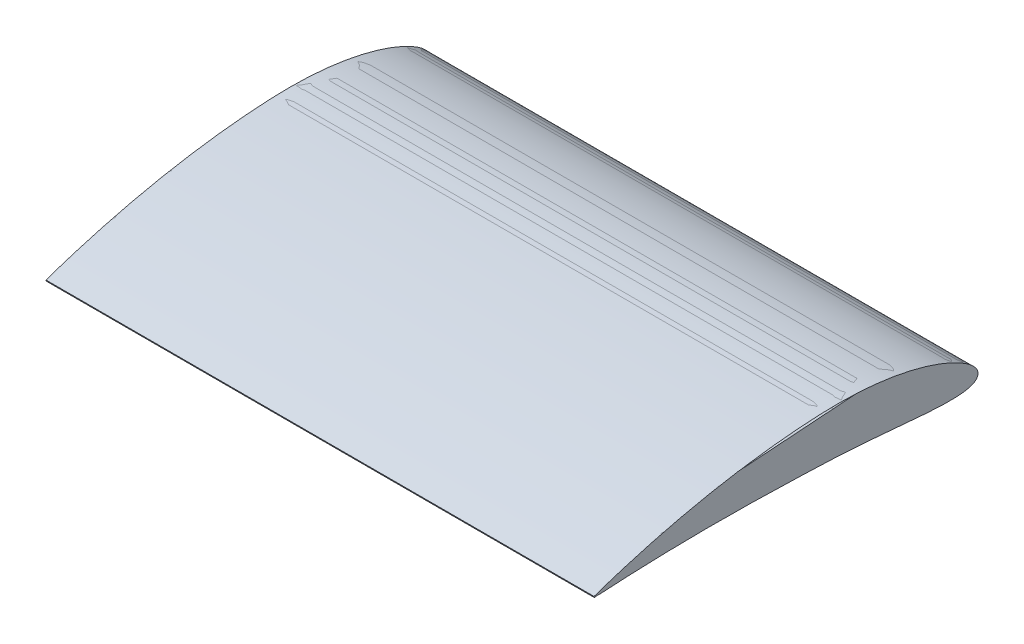
SolidWorks part; units mm, degrees
other "Markup1"
sketch "Sketch2" plane through (-254, -8.3615, 356.0294) normal (-0.9998, -0.003, 0.0177) x (0.0176, 0.0231, 0.9996)
material "E-Glass Fiber Real"
ref_plane "Front Plane" through (0, 0, 0) normal (0, 0, 1) x (1, 0, 0)
ref_plane "Top Plane" through (0, 0, 0) normal (0, 1, 0) x (1, 0, 0)
ref_plane "Right Plane" through (0, 0, 0) normal (1, 0, 0) x (0, 0, -1)
curve "Curve1"
  spline degree 3 poles (0, 0.0012, 1.0003) (0, 0.0015, 0.9994) (0, 0.0028, 0.9958) (0, 0.0055, 0.9879) (0, 0.0099, 0.9747) (0, 0.0159, 0.9565) (0, 0.0233, 0.9333) (0, 0.0318, 0.9054) (0, 0.0411, 0.8731) (0, 0.051, 0.8366) (0, 0.0612, 0.7964) (0, 0.0713, 0.7528) (0, 0.0811, 0.7063) (0, 0.0903, 0.6574) (0, 0.0985, 0.6067) (0, 0.1057, 0.5546) (0, 0.1115, 0.5018) (0, 0.1158, 0.4488) (0, 0.1186, 0.3959) (0, 0.1189, 0.3436) (0, 0.1164, 0.2927) (0, 0.1112, 0.2442) (0, 0.1037, 0.1988) (0, 0.0942, 0.157) (0, 0.0831, 0.1194) (0, 0.0711, 0.0865) (0, 0.0584, 0.0585) (0, 0.0457, 0.0357) (0, 0.0334, 0.0184) (0, 0.0218, 0.0064) (0, 0.0108, -0.0005) (0, -0.0003, -0.0011) (0, -0.0092, 0.0055) (0, -0.0148, 0.017) (0, -0.0185, 0.0329) (0, -0.0204, 0.0533) (0, -0.0208, 0.0781) (0, -0.0198, 0.107) (0, -0.0176, 0.1398) (0, -0.0147, 0.176) (0, -0.0111, 0.2153) (0, -0.0074, 0.2574) (0, -0.0037, 0.3019) (0, -0.0005, 0.3484) (0, 0.002, 0.397) (0, 0.0037, 0.4471) (0, 0.0055, 0.4983) (0, 0.0069, 0.5496) (0, 0.0079, 0.6006) (0, 0.0085, 0.6505) (0, 0.0086, 0.699) (0, 0.0083, 0.7455) (0, 0.0076, 0.7894) (0, 0.0065, 0.8302) (0, 0.0053, 0.8675) (0, 0.0039, 0.9007) (0, 0.0027, 0.9296) (0, 0.0013, 0.9539) (0, 0.0006, 0.9727) (0, -0.0011, 0.9872) (0, 0, 0.9944) (0, -0.002, 0.9999) (0, -0.0005, 1) (0, 0, 1) knots 0 0 0 0 0.001372 0.005465 0.012235 0.021602 0.033461 0.047671 0.064081 0.082496 0.102719 0.124527 0.147676 0.171913 0.196978 0.222597 0.248497 0.274385 0.300041 0.32569 0.350525 0.37428 0.396711 0.417577 0.436654 0.453744 0.46868 0.481329 0.491631 0.499616 0.505546 0.510185 0.514824 0.520702 0.528516 0.538466 0.550543 0.564643 0.580638 0.598345 0.617584 0.638174 0.659922 0.682632 0.706121 0.730727 0.7557 0.780732 0.805564 0.829932 0.85357 0.876213 0.89761 0.917519 0.935698 0.951943 0.966047 0.97784 0.987174 0.993932 0.998018 0.999386 1 1 1 1
sketch "Sketch1" plane through (0, 0, 0) normal (1, 0, 0) x (0, 0, -1)
  line L0 (-354.7873, -0.0303) -> (-354.8762, 0.4104)
  line L1 (-354.7873, -0.0303) -> (0.8093, 1.5275) construction
  line L2 (0.8093, 1.5275) -> (0.7921, 5.4415) construction
  line L3 (-354.8867, -0.0431) -> (-354.9915, 0.4765)
  spline S0 degree 1 poles (-354.9915, 0.4765) (-354.8867, -0.0431) knots 0 0 1 1 construction
  spline S1 degree 3 poles (-354.8762, 0.4104) (-354.5599, 0.5194) (-353.2997, 0.9536) (-350.4787, 1.9271) (-345.801, 3.4978) (-336.0241, 6.7216) (-319.6545, 11.7989) (-300.5983, 17.1306) (-282.4229, 21.7243) (-261.1758, 26.6516) (-238.6223, 31.1455) (-208.7748, 36.0048) (-183.9617, 39.0905) (-158.9023, 41.1132) (-140.0967, 42.1114) (-121.5167, 42.2289) (-103.4222, 41.3211) (-86.1884, 39.4787) (-70.0435, 36.8105) (-55.1998, 33.4329) (-41.8434, 29.5109) (-30.1305, 25.2201) (-20.187, 20.7343) (-12.1072, 16.2263) (-5.9269, 11.8553) (-1.6792, 7.7165) (0.7658, 3.7968) (0.9875, -0.1483) (-1.3511, -3.3089) (-5.4508, -5.2881) (-11.0873, -6.5875) (-18.3491, -7.2685) (-27.1638, -7.4049) (-37.4471, -7.0538) (-49.0831, -6.3019) (-61.9524, -5.238) (-75.9299, -3.9839) (-96.4067, -2.1536) (-117.9372, -0.4584) (-140.4848, 0.6745) (-158.2965, 1.2867) (-176.4839, 1.9179) (-200.672, 2.5862) (-224.5411, 2.9791) (-247.8302, 3.0285) (-264.3373, 2.9074) (-279.9331, 2.6564) (-294.438, 2.2829) (-307.6819, 1.8521) (-319.5134, 1.3711) (-329.7674, 0.9129) (-338.3889, 0.4268) (-345.077, 0.1915) (-350.2276, -0.4064) (-352.7802, -0.0354) (-354.7446, -0.7581) (-354.7772, -0.2025) (-354.7873, -0.0303) knots 0 0 0 0 0.001372 0.005465 0.012235 0.021602 0.047671 0.082496 0.102719 0.124527 0.171913 0.196978 0.248497 0.274385 0.300041 0.32569 0.350525 0.37428 0.396711 0.417577 0.436654 0.453744 0.46868 0.481329 0.491631 0.499616 0.505546 0.510185 0.514824 0.520702 0.528516 0.538466 0.550543 0.564643 0.580638 0.598345 0.617584 0.638174 0.682632 0.706121 0.730727 0.7557 0.780732 0.829932 0.85357 0.876213 0.89761 0.917519 0.935698 0.951943 0.966047 0.97784 0.987174 0.993932 0.998018 0.999386 1 1 1 1
  spline S2 degree 3 poles (-354.9915, 0.4765) (-347.7836, 2.9597) (-333.3117, 7.7674) (-304.0781, 16.465) (-267.0965, 25.7748) (-229.6395, 32.9445) (-199.4502, 37.3012) (-176.7143, 39.8272) (-153.9062, 41.5865) (-131.0398, 42.4798) (-108.1542, 41.8638) (-89.1681, 39.9795) (-74.0989, 37.5944) (-62.8814, 35.3319) (-51.7773, 32.562) (-40.8241, 29.2405) (-31.8676, 25.9544) (-24.8509, 22.952) (-19.6856, 20.4844) (-14.6455, 17.7675) (-9.7758, 14.742) (-5.9468, 11.8749) (-3.1406, 9.2694) (-1.2444, 7.1001) (0.0802, 5.0591) (0.7347, 3.2254) (0.9597, 1.7496) (0.8529, 0.2733) (0.1431, -1.5595) (-1.5772, -3.4176) (-4.1427, -4.7763) (-6.8851, -5.694) (-9.6819, -6.3305) (-13.4588, -6.9198) (-18.2203, -7.308) (-23.9414, -7.4643) (-29.6625, -7.4093) (-35.3792, -7.2116) (-41.0906, -6.9122) (-48.6991, -6.4144) (-58.1991, -5.6579) (-69.5902, -4.656) (-80.9786, -3.6301) (-92.3689, -2.6278) (-107.5631, -1.3754) (-126.5734, -0.0489) (-145.6132, 0.7575) (-160.8504, 1.2747) (-176.0872, 1.8014) (-195.1363, 2.3454) (-218.0008, 2.7794) (-237.057, 2.9256) (-252.3023, 2.8969) (-263.736, 2.8025) (-275.1687, 2.638) (-286.6002, 2.3917) (-296.1246, 2.1237) (-303.7428, 1.8773) (-309.4566, 1.6726) (-315.1707, 1.4473) (-320.8814, 1.2068) (-326.5862, 0.9549) (-331.3522, 0.7146) (-335.168, 0.5116) (-338.021, 0.3672) (-340.8524, 0.247) (-343.6848, 0.1184) (-346.0992, -0.0683) (-348.0577, -0.2494) (-349.4952, -0.3431) (-350.6418, -0.3458) (-351.5091, -0.2914) (-352.1695, -0.2751) (-352.8786, -0.3248) (-353.5347, -0.4594) (-354.1336, -0.6434) (-354.4711, -0.6994) (-354.7188, -0.6206) (-354.8778, -0.3922) (-354.8788, -0.1783) (-354.8867, -0.0431) knots -0.00012 -0.00012 -0.00012 -0.00012 0.031134 0.062387 0.124894 0.187401 0.218655 0.249908 0.281162 0.312415 0.343669 0.374922 0.390549 0.406176 0.421802 0.437429 0.453056 0.460869 0.468683 0.476496 0.484309 0.492123 0.496029 0.499936 0.503843 0.505796 0.507749 0.509703 0.511656 0.515563 0.519469 0.523376 0.527283 0.53119 0.539003 0.546816 0.55463 0.562443 0.570256 0.57807 0.593696 0.609323 0.62495 0.640577 0.656203 0.687457 0.71871 0.734337 0.749964 0.781217 0.812471 0.843724 0.859351 0.874978 0.890604 0.906231 0.921858 0.929671 0.937485 0.945298 0.953111 0.960925 0.968738 0.972645 0.976552 0.980458 0.984365 0.988272 0.990225 0.992178 0.994132 0.995108 0.996085 0.997062 0.998038 0.998527 0.999015 0.999259 0.999503 0.999992 0.999992 0.999992 0.999992
  dimension "D1" = 355.6
  dimension "D2" = 0.1
extrude "Boss-Extrude1" add sketch "Sketch1" along normal blind 254 and the other way blind 254
